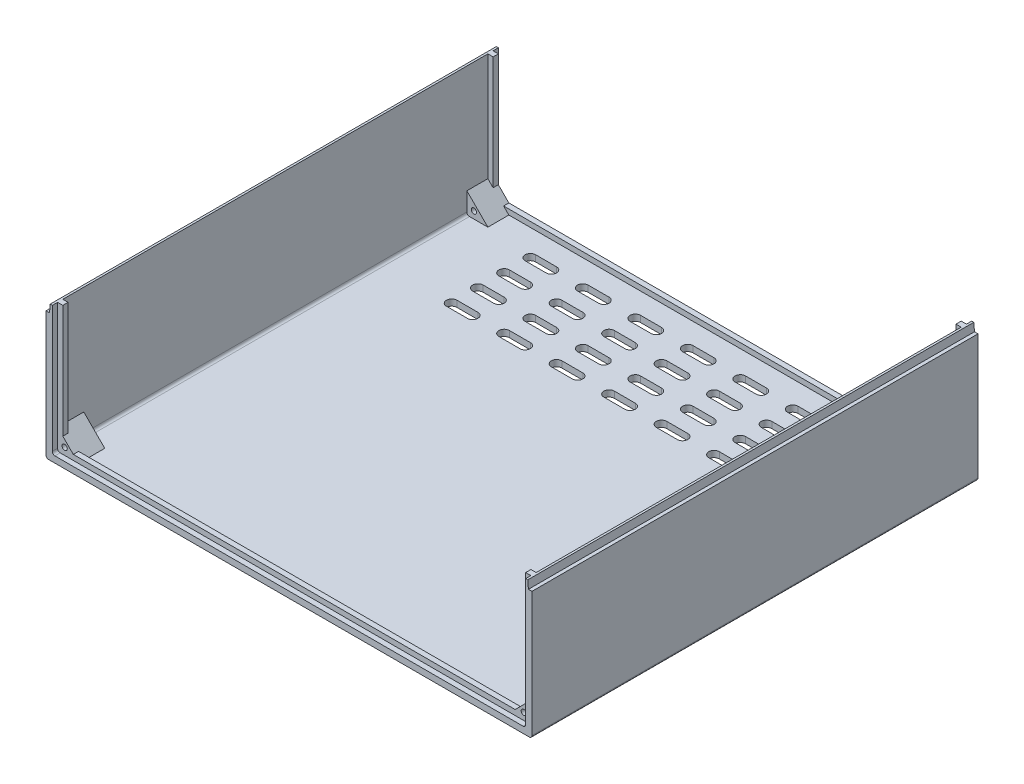
SolidWorks part; units mm, degrees
ref_plane "Спереди" through (0, 0, 0) normal (0, 0, 1) x (1, 0, 0)
ref_plane "Сверху" through (0, 0, 0) normal (0, 1, 0) x (1, 0, 0)
ref_plane "Справа" through (0, 0, 0) normal (1, 0, 0) x (0, 0, -1)
sketch "Эскиз1" plane through (0, 0, 0) normal (0, 0, 1) x (1, 0, 0)
  line L0 (0, 49.2) -> (0, 0)
  line L1 (0, 0) -> (180.4, 0) construction
  line L2 (0, 0) -> (0, 98.4) construction
  line L3 (0, 98.4) -> (180.4, 98.4) construction
  line L4 (180.4, 0) -> (180.4, 98.4) construction
  line L5 (0, 0) -> (180.4, 0)
  line L6 (180.4, 0) -> (180.4, 49.2)
  line L11 (182.8, -2.4) -> (-2.4, -2.4)
  line L16 (0, 8) -> (8, 0)
  line L17 (180.4, 8) -> (172.4, 0)
  line L18 (2.7, 98.4) -> (2.7, 0) construction
  line L19 (177.7, 98.4) -> (177.7, 0) construction
  line L20 (0, 2.7) -> (180.4, 2.7) construction
  line L21 (180.4, 49.2) -> (182.8, 49.2)
  line L22 (182.8, 49.2) -> (182.8, -2.4)
  line L23 (0, 49.2) -> (-2.4, 49.2)
  line L24 (-2.4, 49.2) -> (-2.4, -2.4)
  line L25 (0, 49.2) -> (2, 49.2)
  line L26 (2, 49.2) -> (2, 6)
  line L27 (6, 2) -> (174.4, 2)
  line L28 (180.4, 49.2) -> (178.4, 49.2)
  line L29 (178.4, 49.2) -> (178.4, 6)
  circle A0 centre (177.7, 2.7) radius 1
  circle A1 centre (2.7, 2.7) radius 1
  dimension "D5" = 2
  dimension "D6" = 2
  dimension "D1" = 180.4
  dimension "D2" = 98.4
  dimension "D3" = 2.4
  dimension "D4" = 2.4
  dimension "D7" = 2
  dimension "D8" = 2
  dimension "D9" = 2.4
  dimension "D10" = 2.7
  dimension "D11" = 2.7
  dimension "D12" = 2.7
  dimension "D13" = 8
  dimension "D14" = 8
  dimension "D15" = 8
  dimension "D16" = 8
  dimension "D17" = 2
extrude "Бобышка-Вытянуть1" add sketch "Эскиз1" along normal blind 170 contours L23 L24 L11 L22 L21 L6 L5 L0 region at (-1.9225, 28.6, 0)
extrude "Бобышка-Вытянуть2" add sketch "Эскиз1<3>" along normal blind 10 from offset 2 contours L16 L0 L5 A1 | L6 L17 L5 A0 region at (0.92, 6.92, 0) region at (173.48, 0.92, 0)
sketch "Эскиз1<3>" plane through (0, 0, 0) normal (0, 0, 1) x (1, 0, 0) same geometry as "Эскиз1"
extrude "Бобышка-Вытянуть3" add sketch "Эскиз1<4>" along normal blind 2 from offset 2 contours L28 L29 L17 L6 | L27 L16 L5 L17 | L26 L25 L0 L16 region at (1.0079, 28.0961, 0) region at (90.2, 1.004, 0) region at (179.3921, 28.0961, 0)
sketch "Эскиз1<4>" plane through (0, 0, 0) normal (0, 0, 1) x (1, 0, 0) same geometry as "Эскиз1"
fillet "Скругление1" radius 1 4 edges at (-2.4, -2.4, 85) (182.8, -2.4, 85) (180.4, 0, 1) (0, 0, 1)
extrude "Бобышка-Вытянуть4" add sketch "Эскиз1<5>" along normal blind 10 from offset 158 contours L6 L17 L5 A0 | L16 L0 L5 A1 region at (0.92, 6.92, 0) region at (173.48, 0.92, 0)
sketch "Эскиз1<5>" plane through (0, 0, 0) normal (0, 0, 1) x (1, 0, 0) same geometry as "Эскиз1"
extrude "Бобышка-Вытянуть5" add sketch "Эскиз1<6>" along normal blind 2 from offset 166 contours L28 L29 L17 L6 | L27 L16 L5 L17 | L26 L25 L0 L16 region at (1.0079, 28.0961, 0) region at (90.2, 1.004, 0) region at (179.3921, 28.0961, 0)
sketch "Эскиз1<6>" plane through (0, 0, 0) normal (0, 0, 1) x (1, 0, 0) same geometry as "Эскиз1"
fillet "Скругление2" radius 1 2 edges at (0, 0, 85) (180.4, 0, 85)
sketch "Эскиз2" plane through (0, 49.2, 0) normal (0, 1, 0) x (1, 0, 0)
  line L0 (0, -170) -> (-2.4, -170) construction
  line L1 (-2.4, 0) -> (-1.1, 0)
  line L2 (-2.4, 0) -> (-2.4, -170)
  line L3 (-2.4, -170) -> (-1.1, -170)
  line L4 (-1.1, 0) -> (-1.1, -170)
  line L5 (180.4, -170) -> (182.8, -170) construction
  line L6 (182.8, 0) -> (181.5, 0)
  line L7 (182.8, 0) -> (182.8, -170)
  line L8 (182.8, -170) -> (181.5, -170)
  line L9 (181.5, 0) -> (181.5, -170)
  dimension "D1" = 1.3
  dimension "D2" = 1.3
extrude "Вырез-Вытянуть1" cut sketch "Эскиз2" against normal blind 3
chamfer "Фаска1" distance 0.3 angle 85 2 edges at (181.5, 49.2, 85) (-1.1, 49.2, 85) first distance on face at (179.9167, 49.2, 85) first distance on face at (0.4833, 49.2, 85)
fillet "Скругление3" radius 1 2 edges at (0, 0, 169) (180.4, 0, 169)
sketch "Эскиз3" plane through (0, 0, 0) normal (0, 1, 0) x (1, 0, 0)
  line L0 (1, -14) -> (179.4, -14) construction
  line L1 (1, -12) -> (1, -158) construction
  line L2 (179.4, -158) -> (179.4, -12) construction
  line L3 (6, -4) -> (174.4, -4) construction
  line L4 (86.2, -14) -> (94.2, -14) construction
  line L5 (86.2, -12) -> (94.2, -12)
  line L6 (86.2, -16) -> (94.2, -16)
  arc A0 (86.2, -12) -> (86.2, -16) centre (86.2, -14) ccw
  arc A1 (94.2, -16) -> (94.2, -12) centre (94.2, -14) ccw
  point P10 (90.2, -14)
  dimension "D1" = 10
  dimension "D2" = 8
  dimension "D3" = 4
extrude "Вырез-Вытянуть2" cut sketch "Эскиз3" against normal through all
pattern_linear "Линейный массив1" count 4 spacing 10 along (0, 0, 1) of "Вырез-Вытянуть2"
pattern_linear "Линейный массив2" count 4 spacing 20 along (-1, 0, 0) of "Линейный массив1"
pattern_linear "Линейный массив3" count 4 spacing 20 along (1, 0, 0) of "Линейный массив1"
